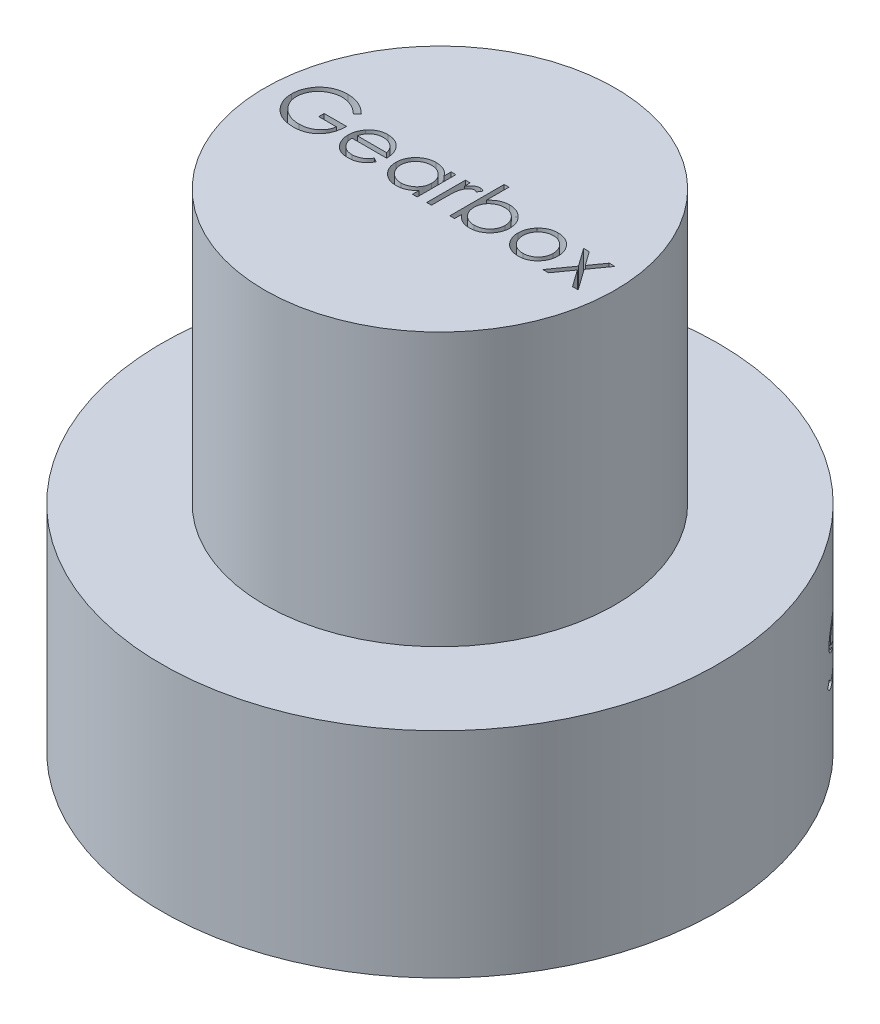
SolidWorks part; units mm, degrees
ref_plane "정면" through (0, 0, 0) normal (0, 0, 1) x (1, 0, 0)
ref_plane "윗면" through (0, 0, 0) normal (0, 1, 0) x (1, 0, 0)
ref_plane "우측면" through (0, 0, 0) normal (1, 0, 0) x (0, 0, -1)
sketch "Sketch1" plane through (0, 0, 0) normal (0, 1, 0) x (1, 0, 0)
  circle A0 centre (0, 0) radius 63
extrude "Boss-Extrude1" add sketch "Sketch1" along normal blind 98
sketch "Sketch2" plane through (0, 98, 0) normal (0, 1, 0) x (1, 0, 0)
  text T0 "Gearbox" font "Century Gothic" height in points 72
extrude "Cut-Extrude1" cut sketch "Sketch2" against normal blind 30
sketch "Sketch3" plane through (0, 0, 0) normal (0, -1, 0) x (1, 0, 0)
  circle A0 centre (0, 0) radius 100
extrude "Boss-Extrude2" add sketch "Sketch3" along normal blind 77
ref_plane "Plane1" through (0, 0, -100) normal (0, 0, 1) x (1, 0, 0)
sketch "Sketch4" plane through (0, 0, -100) normal (0, 0, 1) x (1, 0, 0)
  text T0 "Scatter Shield" font "Century Gothic" height in points 72
extrude "Cut-Extrude2" cut sketch "Sketch4" along normal blind 77
